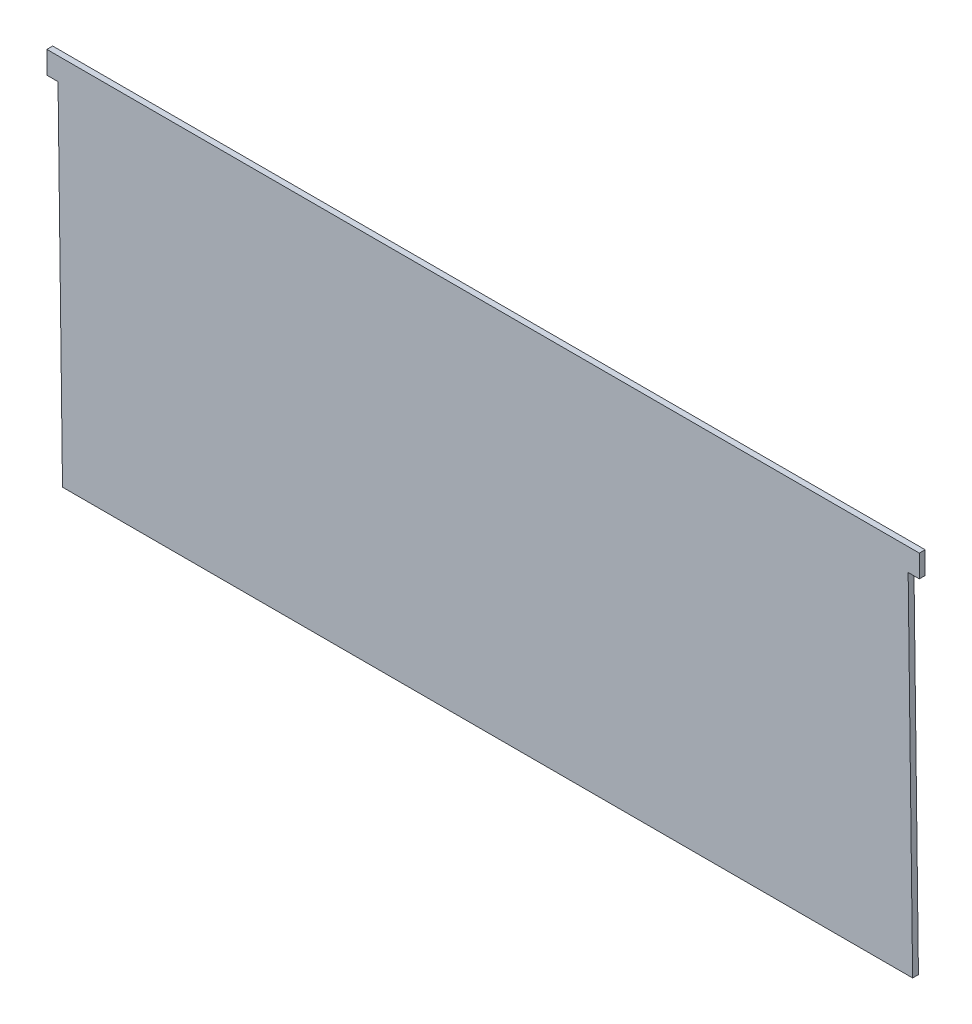
SolidWorks part; units mm, degrees
ref_plane "Alzado" through (0, 0, 0) normal (0, 0, 1) x (1, 0, 0)
ref_plane "Planta" through (0, 0, 0) normal (0, 1, 0) x (1, 0, 0)
ref_plane "Vista lateral" through (0, 0, 0) normal (1, 0, 0) x (0, 0, -1)
sketch "Sketch1" plane through (0, 0, 0) normal (0, 0, 1) x (1, 0, 0)
  line L0 (-3.5, 110.115) -> (-1, 110.115)
  line L1 (0, 32.1214) -> (190, 32.1214)
  line L2 (0, 32.1214) -> (-1, 110.115)
  line L4 (190, 32.1214) -> (189, 110.1214)
  line L14 (-3.5, 110.115) -> (-3.5, 115.115)
  line L15 (-3.5, 115.115) -> (191.5, 115.115)
  line L16 (191.5, 110.115) -> (191.5, 115.115)
  line L18 (189, 110.1214) -> (191.5, 110.115)
extrude "Boss-Extrude1" add sketch "Sketch1" along normal blind 1.3
sketch "Sketch2" plane through (-0.0037, 110.1151, 0) normal (0, 1, 0) x (1, 0, 0)
  line L0 (-0.9963, -1.3) -> (-0.9963, 0) construction
  line L1 (-0.9963, -0.65) -> (189.0037, -0.65) construction
